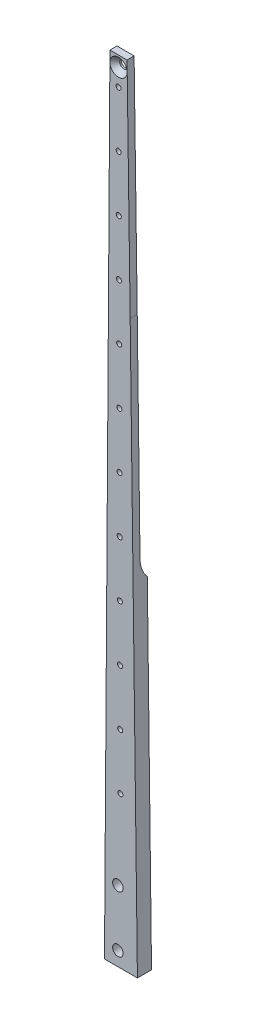
SolidWorks part; units mm, degrees
ref_plane "XY" through (0, 0, 0) normal (0, 0, 1) x (1, 0, 0)
ref_plane "XZ" through (0, 0, 0) normal (0, 1, 0) x (1, 0, 0)
ref_plane "YZ" through (0, 0, 0) normal (1, 0, 0) x (0, 0, -1)
ref_axis "X" through (-4.8636, 0, 0) along (1, 0, 0)
ref_axis "Y" through (0, -19.9998, 0) along (0, 1, 0)
ref_axis "Z" through (0, 0, 6.7699) along (0, 0, -1)
sketch "Sketch3" plane through (0, 0, 0) normal (0, 0, 1) x (1, 0, 0)
  line B0 (6.1442, 399.996) -> (-1.5646, 399.996)
  arc B1 (10.9787, 29.7914) -> (-4.1092, 31.483) centre (0, 0) ccw
  spline B2 degree 3 poles (-2.2314, 299.996) (-2.2349, 299.49) (-2.393, 276.4245) (-2.5531, 253.359) (-2.8683, 208.24) (-3.0269, 185.6805) (-3.3464, 140.3) (-3.6556, 96.4207) (-3.9627, 52.5413) (-4.1092, 31.483) knots 0 0 0 0 0.005653 0.257702 0.257702 0.509751 0.509751 0.764723 1 1 1 1
  spline B3 degree 3 poles (-1.5646, 399.996) (-1.6372, 388.7162) (-1.7108, 377.4364) (-1.931, 344.1246) (-2.0802, 322.0711) (-2.2313, 300.0175) (-2.2314, 299.996) knots 0 0 0 0 0.338393 0.338393 0.999354 1 1 1 1
  spline B4 degree 3 poles (7.5462, 299.996) (7.092, 333.3295) (6.6238, 366.6628) (6.1442, 399.996) knots 0 0 0 0 1 1 1 1
  spline B5 degree 3 poles (10.9787, 29.7914) (9.9109, 119.8606) (8.7733, 209.9289) (7.5462, 299.996) knots 0 0 0 0 1 1 1 1
sketch_block_instance "Block-RearSpar-1"
sketch_block "Block-RearSpar"
sketch "Sketch4" plane through (0, 0, 0) normal (0, 0, 1) x (1, 0, 0)
  line L2 (6.1442, 399.996) -> (-1.5646, 399.996) construction
  line L3 (6.1442, 399.996) -> (-1.5646, 399.996)
  arc A0 (10.9787, 29.7914) -> (-4.1092, 31.483) centre (0, 0) ccw construction
  arc A1 (10.9787, 29.7914) -> (-4.1092, 31.483) centre (0, 0) ccw
  spline S2 degree 3 poles (-121.6535, 2293.9975) (5.1575, 1627.3849) (2.2169, 940.3657) (-2.5531, 253.359) (-2.8683, 208.24) (-3.0269, 185.6805) (-3.3464, 140.3) (-8.3535, -570.1873) (-12.8071, -1280.6785) (-1.472, -1968.4561) knots -7.417974 -7.417974 -7.417974 -7.417974 0.005653 0.257702 0.257702 0.509751 0.509751 0.764723 8.447775 8.447775 8.447775 8.447775 only from (-2.2314, 299.996) to (-4.1092, 31.483) construction
  spline S3 degree 3 poles (-46.2092, 2399.0845) (3.9416, 1721.255) (2.6931, 1043.695) (-1.931, 344.1246) (-5.1261, -128.2574) (-9.209, -600.6333) (-435.2561, -1640.5057) knots -19.987749 -19.987749 -19.987749 -19.987749 0.338393 0.338393 0.999354 14.509863 14.509863 14.509863 14.509863 only from (-1.5646, 399.996) to (-2.2314, 299.996) construction
  spline S4 degree 3 poles (-2.9312, -1699.8175) (44.279, -332.5444) (-19.8869, 1033.1673) (-15.4341, 2399.841) knots -19.992737 -19.992737 -19.992737 -19.992737 20.997545 20.997545 20.997545 20.997545 only from (7.5462, 299.996) to (6.1442, 399.996) construction
  spline S5 degree 3 poles (31.3042, -1970.0909) (13.5099, -546.9668) (15.0768, 876.6883) (-42.477, 2299.3052) knots -7.401386 -7.401386 -7.401386 -7.401386 8.400667 8.400667 8.400667 8.400667 only from (10.9787, 29.7914) to (7.5462, 299.996) construction
  spline S6 degree 3 poles (-2.2314, 299.996) (-2.2349, 299.49) (-2.393, 276.4245) (-2.5531, 253.359) (-2.8683, 208.24) (-3.0269, 185.6805) (-3.3464, 140.3) (-3.6556, 96.4207) (-3.9627, 52.5413) (-4.1092, 31.483) knots 0 0 0 0 0.005653 0.257702 0.257702 0.509751 0.509751 0.764723 1 1 1 1
  spline S7 degree 3 poles (-1.5646, 399.996) (-1.6372, 388.7162) (-1.7108, 377.4364) (-1.931, 344.1246) (-2.0802, 322.0711) (-2.2313, 300.0175) (-2.2314, 299.996) knots 0 0 0 0 0.338393 0.338393 0.999354 1 1 1 1
  spline S8 degree 3 poles (7.5462, 299.996) (7.092, 333.3295) (6.6238, 366.6628) (6.1442, 399.996) knots 0 0 0 0 1 1 1 1
  spline S9 degree 3 poles (10.9787, 29.7914) (9.9109, 119.8606) (8.7733, 209.9289) (7.5462, 299.996) knots 0 0 0 0 1 1 1 1
extrude "Boss-Extrude2" add sketch "Sketch4" along normal blind 6.35
sketch "Sketch5" plane through (0, 0, 0) normal (0, 0, 1) x (1, 0, 0)
  line L0 (0, 44.45) -> (0, 0) construction
  line L1 (-12.7, 0) -> (12.7, 0)
  line L2 (-12.7, 0) -> (-12.7, 44.45)
  line L4 (12.7, 0) -> (12.7, 44.45)
  line L13 (12.7, 44.45) -> (-12.7, 44.45)
  circle A1 centre (0, 0) radius 31.75 construction
  dimension "D1" = 25.4
  dimension "D2" = 44.45
extrude "Cut-Extrude1" cut sketch "Sketch5" along normal through all
hole_wizard "3/16 (0.1875) Dowel Hole1" positions "Sketch7" profile "Sketch8" hole size "3/16" standard "ANSI Inch"
sketch "Sketch7" plane through (0, 0, 6.35) normal (0, 0, 1) x (1, 0, 0)
  line L0 (2.032, 76.2) -> (2.032, 50.8) construction
  line L1 (2.032, 50.8) -> (2.032, 44.45) construction
  line L3 (10.8043, 44.45) -> (-4.0189, 44.45) construction
  line L4 (2.032, 44.45) -> (0, 0)
  point P0 (2.032, 50.8)
  point P2 (2.032, 76.2)
  dimension "D1" = 25.4
  dimension "D2" = 6.35
  dimension "D3" = 2.032
sketch "Sketch8" plane through (2.032, 50.8, 6.35) normal (1, 0, 0) x (0, -1, 0)
  line L0 (0, 0) -> (0, 12.0988)
  line L1 (0, 12.0988) -> (2.3812, 10.668)
  line L2 (2.3812, 10.668) -> (2.3812, 0)
  line L5 (2.3812, 0) -> (0, 0)
  line L10 (0, 12.0988) -> (-2.3813, 10.668) construction
  line L11 (0, -6.35) -> (0, 107.95) construction
  dimension "Hole Dia." = 4.7625
  dimension "Hole Depth" = 10.668
  dimension "Drill Angle" = 118
hole_wizard "CSK for #6 Flat Head Socket Cap Screw1" positions "Sketch10" profile "Sketch11" countersink size "#6" standard "ANSI Inch" end condition through all
sketch "Sketch10" plane through (0, 0, 6.35) normal (0, 0, -1) x (-1, 0, 0)
  line L0 (-2.2898, 399.996) -> (-2.2898, 395.2335)
  line L1 (-6.1442, 399.996) -> (1.5646, 399.996) construction
  point P2 (-2.2898, 395.2335)
  dimension "D1" = 4.7625
sketch "Sketch11" plane through (2.2898, 395.2335, 6.35) normal (1, 0, 0) x (0, -1, 0)
  line L0 (0, 0) -> (0, 6.35)
  line L1 (0, 6.35) -> (1.8288, 6.35)
  line L2 (1.8288, 6.35) -> (1.8288, 2.3814)
  line L3 (1.8288, 2.3814) -> (3.8989, 0)
  line L5 (3.8989, 0) -> (0, 0)
  line L6 (-1.8288, 2.3814) -> (-3.8989, 0) construction
  line L11 (0, -6.35) -> (0, 107.95) construction
  dimension "Thru Hole Dia." = 3.6576
  dimension "Thru Hole Depth" = 6.35
  dimension "Near C'Sink Dia." = 7.7978
  dimension "Near C'Sink Angle" = 82
sketch "Sketch12" plane through (0, 0, 0) normal (0, 0, -1) x (-1, 0, 0)
  line L0 (-6.1442, 399.996) -> (1.5646, 399.996) construction
  line L1 (13.3747, 196.796) -> (-18.6195, 196.796)
  line L2 (13.3747, 196.796) -> (13.3747, 399.996)
  line L3 (13.3747, 399.996) -> (-18.6195, 399.996)
  line L4 (-18.6195, 196.796) -> (-18.6195, 399.996)
  dimension "D1" = 203.2
extrude "Cut-Extrude2" cut sketch "Sketch12" against normal blind 3.175
fillet "Fillet1" radius 12.7 1 edges at (2.9826, 196.796, 3.175)
hole_wizard "#4-40 Tapped Hole1" positions "Sketch13" profile "Sketch14" tap size "#4-40" standard "ANSI Inch" end condition through all
sketch "Sketch13" plane through (0, 0, 6.35) normal (0, 0, 1) x (1, 0, 0)
  line L0 (2.2898, 399.996) -> (3.3927, 44.45) construction
  line L1 (6.1442, 399.996) -> (-1.5646, 399.996) construction
  line L2 (10.8043, 44.45) -> (-4.0189, 44.45) construction
  point P0 (2.2898, 387.496)
  point P11 (2.2898, 385.7564)
  dimension "D1" = 12.5
sketch "Sketch14" plane through (2.2898, 387.496, 6.35) normal (1, 0, 0) x (0, -1, 0)
  line L0 (0, 0) -> (0, 7.066)
  line L1 (0, 7.066) -> (1.1303, 7.066)
  line L2 (1.1303, 7.066) -> (1.1303, 0)
  line L5 (1.1303, 0) -> (0, 0)
  line L11 (0, -6.35) -> (0, 107.95) construction
  dimension "Thru Tap Drill Dia." = 2.2606
  dimension "Thru Tap Drill Depth" = 7.066
cosmetic thread "Hole Thread1" parameters "D2"=2.8448
pattern_linear "LPattern1" count 12 spacing 25 along (0.0031, -1, 0) of "#4-40 Tapped Hole1"
cosmetic thread "Hole Thread2" parameters "D2"=2.8448
cosmetic thread "Hole Thread3" parameters "D2"=2.8448
cosmetic thread "Hole Thread4" parameters "D2"=2.8448
cosmetic thread "Hole Thread5" parameters "D2"=2.8448
cosmetic thread "Hole Thread6" parameters "D2"=2.8448
cosmetic thread "Hole Thread7" parameters "D2"=2.8448
cosmetic thread "Hole Thread8" parameters "D2"=2.8448
cosmetic thread "Hole Thread9" parameters "D2"=2.8448
cosmetic thread "Hole Thread10" parameters "D2"=2.8448
cosmetic thread "Hole Thread11" parameters "D2"=2.8448
cosmetic thread "Hole Thread12" parameters "D2"=2.8448
